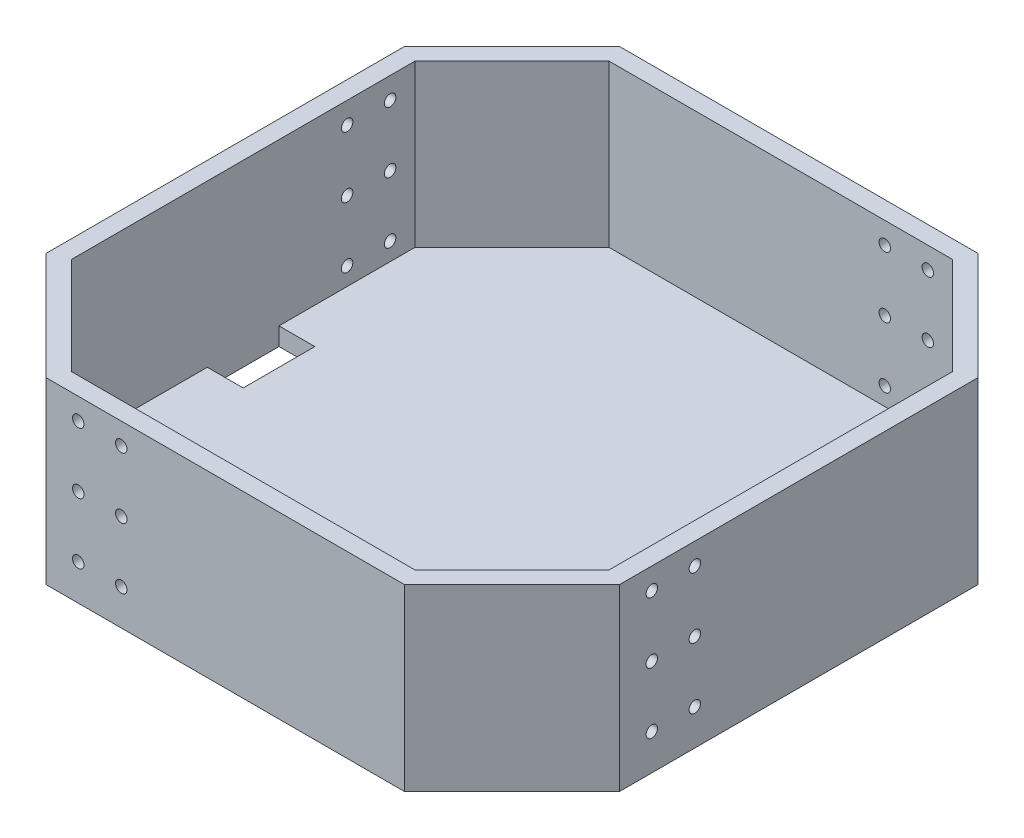
SolidWorks part; units mm, degrees
ref_plane "Front Plane" through (0, 0, 0) normal (0, 0, 1) x (1, 0, 0)
ref_plane "Top Plane" through (0, 0, 0) normal (0, 1, 0) x (1, 0, 0)
ref_plane "Right Plane" through (0, 0, 0) normal (1, 0, 0) x (0, 0, -1)
sketch "Sketch1" plane through (0, 0, 0) normal (0, 1, 0) x (1, 0, 0)
  line L0 (-80, 50) -> (-50, 80)
  line L1 (-80, 80) -> (80, 80)
  line L2 (-80, 80) -> (-80, -80)
  line L3 (-80, -80) -> (80, -80)
  line L4 (80, 80) -> (80, -80)
  line L5 (-80, 80) -> (80, -80) construction
  line L6 (-80, -80) -> (80, 80) construction
  line L7 (50, 80) -> (80, 50)
  line L8 (80, -50) -> (50, -80)
  line L9 (-50, -80) -> (-80, -50)
  point P0 (0, 0)
  point P11 (0, 0)
  point P14 (0, 0)
  point P17 (0, 0)
  point P20 (0, 0)
  dimension "D1" = 160
  dimension "D2" = 45
  dimension "D3" = 30
  dimension "D4" = 4
extrude "Boss-Extrude1" add sketch "Sketch1" along normal blind 50 contours L9 L3 L8 L4 L7 L1 L0 L2 region at (0, 0, 0)
shell "Shell1" thickness 5 removed face at (0, 50, 0)
sketch "Sketch5" plane through (0, 5, 0) normal (0, 1, 0) x (1, 0, 0)
  line L0 (-75, 47.9289) -> (-75, -47.9289) construction
  line L1 (-75, 10) -> (-65, 10)
  line L2 (-75, 10) -> (-75, -10)
  line L3 (-75, -10) -> (-65, -10)
  line L4 (-65, 10) -> (-65, -10)
  point P4 (-75, 0)
  point P7 (-75, 0)
  dimension "D1" = 20
  dimension "D2" = 10
extrude "Cut-Extrude1" cut sketch "Sketch5" against normal up to surface (5 mm away) up to face at (0, 0, 0)
sketch "Sketch6" plane through (0, 0, 80) normal (0, 0, 1) x (1, 0, 0)
  circle A0 centre (-29, 10) radius 1.6 construction
  circle A1 centre (-41, 10) radius 1.6 construction
  circle A2 centre (-29, 27) radius 1.6 construction
  circle A3 centre (-41, 27) radius 1.6 construction
  circle A4 centre (-29, 44) radius 1.6 construction
  circle A5 centre (-41, 44) radius 1.6 construction
  circle A6 centre (-29, 10) radius 1.6
  circle A7 centre (-41, 10) radius 1.6
  circle A8 centre (-29, 27) radius 1.6
  circle A9 centre (-41, 27) radius 1.6
  circle A10 centre (-29, 44) radius 1.6
  circle A11 centre (-41, 44) radius 1.6
extrude "Cut-Extrude2" cut sketch "Sketch6" against normal up to surface (5 mm away) up to face at (0, 27.5, 75)
ref_axis "Axis1" through (0, 52.5, 0) along (0, -1, 0)
pattern_circular "CirPattern1" count 4 every 90 about axis through (0, 52.5, 0) along (0, -1, 0) of "Cut-Extrude2"
